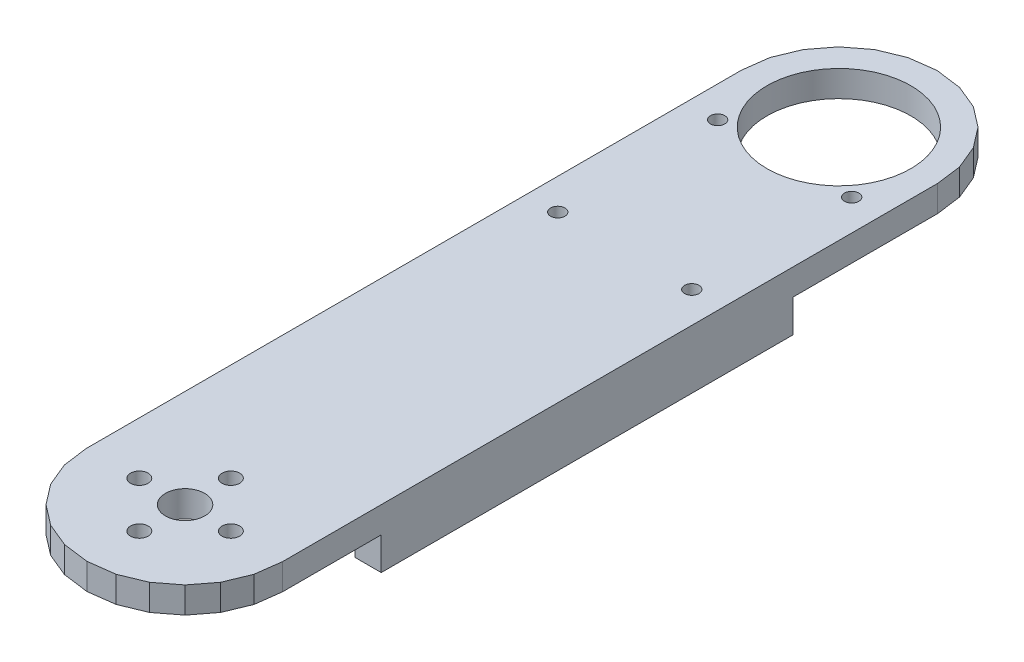
SolidWorks part; units mm, degrees
ref_plane "Front Plane" through (0, 0, 0) normal (0, 0, 1) x (1, 0, 0)
ref_plane "Top Plane" through (0, 0, 0) normal (0, 1, 0) x (1, 0, 0)
ref_plane "Right Plane" through (0, 0, 0) normal (1, 0, 0) x (0, 0, -1)
ref_plane "PY_m20_000" through (0, -20, 0) normal (0, 1, 0) x (1, 0, 0)
sketch "S_prism1" plane through (0, -20, 0) normal (0, 1, 0) x (1, 0, 0)
  line L0 (-15, -0.1) -> (-14.492, -3.956)
  line L1 (-14.492, -3.956) -> (-13.004, -7.55)
  line L2 (-13.004, -7.55) -> (-10.636, -10.636)
  line L3 (-10.636, -10.636) -> (-7.55, -13.004)
  line L4 (-7.55, -13.004) -> (-3.956, -14.492)
  line L5 (-3.956, -14.492) -> (-0.1, -15)
  line L6 (-0.1, -15) -> (0.1, -15)
  line L7 (0.1, -15) -> (3.956, -14.492)
  line L8 (3.956, -14.492) -> (7.55, -13.004)
  line L9 (7.55, -13.004) -> (10.636, -10.636)
  line L10 (10.636, -10.636) -> (13.004, -7.55)
  line L11 (13.004, -7.55) -> (14.492, -3.956)
  line L12 (14.492, -3.956) -> (15, -0.1)
  line L13 (15, -0.1) -> (15, 100.1)
  line L14 (15, 100.1) -> (14.492, 103.956)
  line L15 (14.492, 103.956) -> (13.004, 107.55)
  line L16 (13.004, 107.55) -> (10.636, 110.636)
  line L17 (10.636, 110.636) -> (7.55, 113.004)
  line L18 (7.55, 113.004) -> (3.956, 114.492)
  line L19 (3.956, 114.492) -> (0.1, 115)
  line L20 (0.1, 115) -> (-0.1, 115)
  line L21 (-0.1, 115) -> (-3.956, 114.492)
  line L22 (-3.956, 114.492) -> (-7.55, 113.004)
  line L23 (-7.55, 113.004) -> (-10.636, 110.636)
  line L24 (-10.636, 110.636) -> (-13.004, 107.55)
  line L25 (-13.004, 107.55) -> (-14.492, 103.956)
  line L26 (-14.492, 103.956) -> (-15, 100.1)
  line L27 (-15, 100.1) -> (-15, -0.1)
  dimension "P1" = 15
  dimension "P2" = 0.1
  dimension "P3" = 14.492
  dimension "P4" = 3.956
  dimension "P5" = 13.004
  dimension "P6" = 7.55
  dimension "P7" = 10.636
  dimension "P8" = 10.636
  dimension "P9" = 7.55
  dimension "P10" = 13.004
  dimension "P11" = 3.956
  dimension "P12" = 14.492
  dimension "P13" = 0.1
  dimension "P14" = 15
  dimension "P15" = 0.1
  dimension "P16" = 15
  dimension "P17" = 3.956
  dimension "P18" = 14.492
  dimension "P19" = 7.55
  dimension "P20" = 13.004
  dimension "P21" = 10.636
  dimension "P22" = 10.636
  dimension "P23" = 13.004
  dimension "P24" = 7.55
  dimension "P25" = 14.492
  dimension "P26" = 3.956
  dimension "P27" = 15
  dimension "P28" = 0.1
  dimension "P29" = 15
  dimension "P30" = 100.1
  dimension "P31" = 14.492
  dimension "P32" = 103.956
  dimension "P33" = 13.004
  dimension "P34" = 107.55
  dimension "P35" = 10.636
  dimension "P36" = 110.636
  dimension "P37" = 7.55
  dimension "P38" = 113.004
  dimension "P39" = 3.956
  dimension "P40" = 114.492
  dimension "P41" = 0.1
  dimension "P42" = 115
  dimension "P43" = 0.1
  dimension "P44" = 115
  dimension "P45" = 3.956
  dimension "P46" = 114.492
  dimension "P47" = 7.55
  dimension "P48" = 113.004
  dimension "P49" = 10.636
  dimension "P50" = 110.636
  dimension "P51" = 13.004
  dimension "P52" = 107.55
  dimension "P53" = 14.492
  dimension "P54" = 103.956
  dimension "P55" = 15
  dimension "P56" = 100.1
extrude "Boss_1" add sketch "S_prism1" along normal blind 4
ref_plane "PZ_m78_000" through (0, 0, -78) normal (0, 0, 1) x (1, 0, 0)
sketch "S_box2" plane through (0, 0, -78) normal (0, 0, 1) x (1, 0, 0)
  line L0 (-15, -25) -> (-11, -25)
  line L1 (-11, -25) -> (-11, -19.5)
  line L2 (-11, -19.5) -> (-15, -19.5)
  line L3 (-15, -19.5) -> (-15, -25)
  dimension "P1" = 15
  dimension "P2" = 25
  dimension "P3" = 11
  dimension "P4" = 25
  dimension "P5" = 11
  dimension "P6" = 19.5
  dimension "P7" = 15
  dimension "P8" = 19.5
extrude "Boss_2" add sketch "S_box2" along normal blind 63
sketch "S_box3" plane through (0, 0, -78) normal (0, 0, 1) x (1, 0, 0)
  line L0 (11, -25) -> (15, -25)
  line L1 (15, -25) -> (15, -19.5)
  line L2 (15, -19.5) -> (11, -19.5)
  line L3 (11, -19.5) -> (11, -25)
  dimension "P1" = 11
  dimension "P2" = 25
  dimension "P3" = 15
  dimension "P4" = 25
  dimension "P5" = 15
  dimension "P6" = 19.5
  dimension "P7" = 11
  dimension "P8" = 19.5
extrude "Boss_3" add sketch "S_box3" along normal blind 63
ref_plane "PY_m20_100" through (0, -20.1, 0) normal (0, 1, 0) x (1, 0, 0)
sketch "S_hole4" plane through (0, -20.1, 0) normal (0, 1, 0) x (1, 0, 0)
  circle A0 centre (0, 0) radius 3
  dimension "D1_S_hole4" = 6
extrude "Hole_4" cut sketch "S_hole4" along normal blind 4.2
sketch "S_hole5" plane through (0, -20.1, 0) normal (0, 1, 0) x (1, 0, 0)
  circle A0 centre (7, 0) radius 1.35
  dimension "D1_S_hole5" = 2.7
  dimension "P2" = 7
extrude "Hole_5" cut sketch "S_hole5" along normal blind 4.2
sketch "S_hole6" plane through (0, -20.1, 0) normal (0, 1, 0) x (1, 0, 0)
  circle A0 centre (0, -7) radius 1.35
  dimension "D1_S_hole6" = 2.7
  dimension "P2" = 7
extrude "Hole_6" cut sketch "S_hole6" along normal blind 4.2
sketch "S_hole7" plane through (0, -20.1, 0) normal (0, 1, 0) x (1, 0, 0)
  circle A0 centre (-7, 0) radius 1.35
  dimension "D1_S_hole7" = 2.7
  dimension "P2" = 7
extrude "Hole_7" cut sketch "S_hole7" along normal blind 4.2
sketch "S_hole8" plane through (0, -20.1, 0) normal (0, 1, 0) x (1, 0, 0)
  circle A0 centre (0, 7) radius 1.35
  dimension "D1_S_hole8" = 2.7
  dimension "P2" = 7
extrude "Hole_8" cut sketch "S_hole8" along normal blind 4.2
sketch "S_hole9" plane through (0, -20.1, 0) normal (0, 1, 0) x (1, 0, 0)
  circle A0 centre (0, 100) radius 11
  dimension "D1_S_hole9" = 22
  dimension "P2" = 100
extrude "Hole_9" cut sketch "S_hole9" along normal blind 4.2
sketch "S_hole10" plane through (0, -20.1, 0) normal (0, 1, 0) x (1, 0, 0)
  circle A0 centre (-10.25, 91.7) radius 1.1
  dimension "D1_S_hole10" = 2.2
  dimension "P2" = 10.25
  dimension "P3" = 91.7
extrude "Hole_10" cut sketch "S_hole10" along normal blind 4.2
sketch "S_hole11" plane through (0, -20.1, 0) normal (0, 1, 0) x (1, 0, 0)
  circle A0 centre (10.25, 91.7) radius 1.1
  dimension "D1_S_hole11" = 2.2
  dimension "P2" = 10.25
  dimension "P3" = 91.7
extrude "Hole_11" cut sketch "S_hole11" along normal blind 4.2
sketch "S_hole12" plane through (0, -20.1, 0) normal (0, 1, 0) x (1, 0, 0)
  circle A0 centre (-10.25, 67.25) radius 1.1
  dimension "D1_S_hole12" = 2.2
  dimension "P2" = 10.25
  dimension "P3" = 67.25
extrude "Hole_12" cut sketch "S_hole12" along normal blind 4.2
sketch "S_hole13" plane through (0, -20.1, 0) normal (0, 1, 0) x (1, 0, 0)
  circle A0 centre (10.25, 67.25) radius 1.1
  dimension "D1_S_hole13" = 2.2
  dimension "P2" = 10.25
  dimension "P3" = 67.25
extrude "Hole_13" cut sketch "S_hole13" along normal blind 4.2
equation "\"plate_t\" = 3"
equation "\"clearance\" = 0.4"
